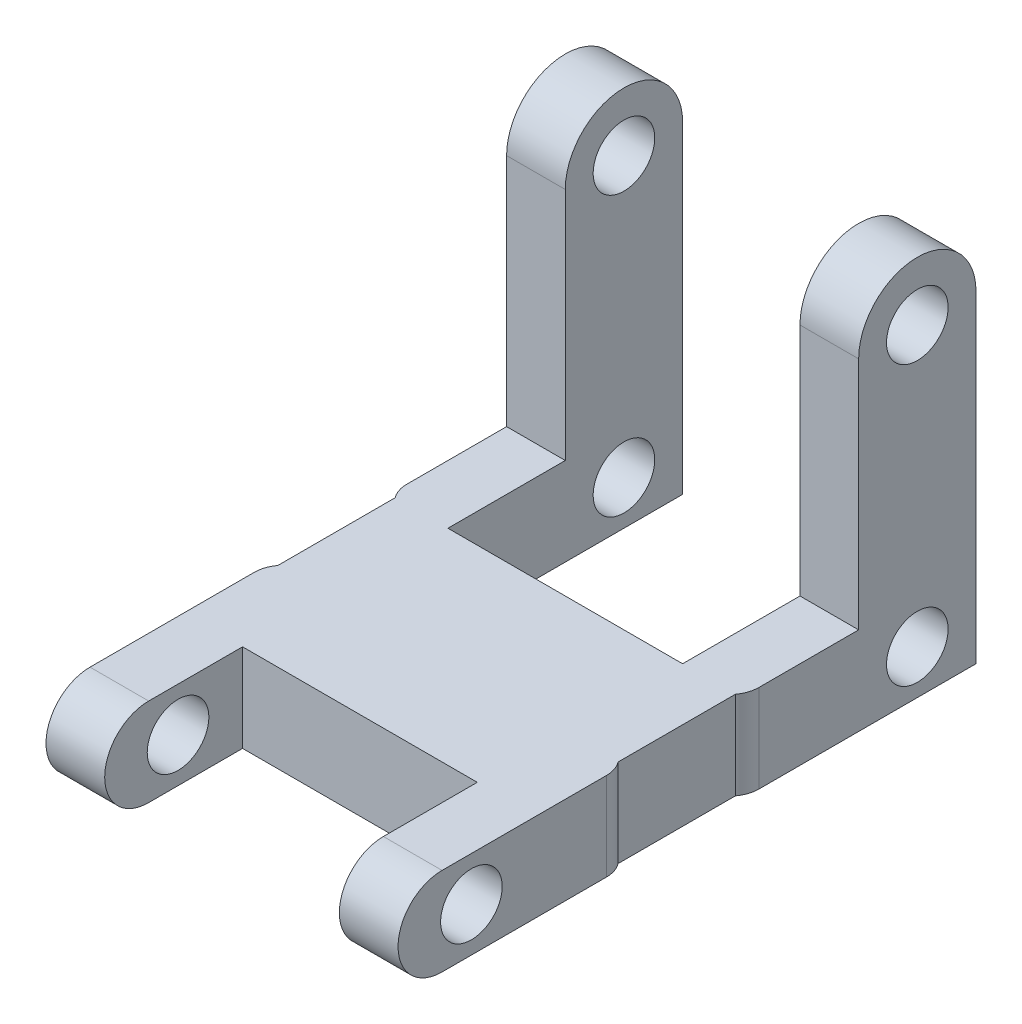
SolidWorks part; units mm, degrees
ref_plane "前视基准面" through (0, 0, 0) normal (0, 0, 1) x (1, 0, 0)
ref_plane "上视基准面" through (0, 0, 0) normal (0, 1, 0) x (1, 0, 0)
ref_plane "右视基准面" through (0, 0, 0) normal (1, 0, 0) x (0, 0, -1)
other "Configuration Table"
sketch "草图1" plane through (0, 0, 0) normal (0, 1, 0) x (1, 0, 0)
  line L0 (-6, 0) -> (6, 0)
  line L1 (-6, 0) -> (-6, -8.7)
  line L2 (-6, -8.7) -> (-4, -8.7)
  line L3 (-4, -8.7) -> (-4, -3)
  line L4 (-4, -3) -> (4, -3)
  line L5 (4, -3) -> (4, -8.7)
  line L6 (4, -8.7) -> (6, -8.7)
  line L7 (6, -8.7) -> (6, 0)
  point P4 (0, 0)
  dimension "D1" = 8.7
  dimension "D2" = 2
  dimension "D3" = 5.7
  dimension "D4" = 8
  dimension "D5" = 5.7
  dimension "D6" = 5.7
  dimension "D7" = 8.7
  dimension "D8" = 2
extrude "凸台-拉伸1" add sketch "草图1" along normal blind 3
sketch "草图2" plane through (-6, 0, 0) normal (-1, 0, 0) x (0, 0, 1)
  line L2 (6.2, 3) -> (0, 3)
  line L3 (0, 3) -> (0, 0)
  line L4 (0, 0) -> (6.2, 0)
  arc A0 (6.2, 0) -> (6.2, 3) centre (6.2, 1.5) ccw
  dimension "D2" = 3
  dimension "D1" = 1.5
  dimension "D3" = 6.2
extrude "切除-拉伸1" cut sketch "草图2" against normal blind 12 flip side to cut
sketch "草图3" plane through (-6, 0, 0) normal (-1, 0, 0) x (0, 0, 1)
  line L0 (6.2, 1.5) -> (5.2, 1.5) construction
  circle A2 centre (5.2, 1.5) radius 1.05
  dimension "D3" = 2.1
  dimension "D2" = 1
extrude "切除-拉伸2" cut sketch "草图3" against normal blind 12
sketch "草图4" plane through (0, 0, 0) normal (0, 0, -1) x (-1, 0, 0)
  line L0 (0, 3) -> (0, 0) construction
  line L1 (-6, 3) -> (6, 3) construction
  circle A0 centre (0, 1.5) radius 0.95
  dimension "D1" = 1.9
extrude "凸台-拉伸2" add sketch "草图4" along normal blind 4
ref_plane "基准面1" through (0, 0, -4) normal (0, 0, -1) x (-1, 0, 0)
sketch "草图5" plane through (0, 0, -4) normal (0, 0, -1) x (-1, 0, 0)
  line L1 (6, 3) -> (6, 0)
  line L15 (6, 3) -> (-6, 3)
  line L16 (-6, 3) -> (-6, 0)
  line L17 (-6, 3) -> (-6, 0) construction
  line L18 (-6, 3) -> (-6, 0) construction
  line L19 (-6, 0) -> (6, 0)
extrude "凸台-拉伸3" add sketch "草图5" along normal blind 8
sketch "草图6" plane through (6, 0, 0) normal (1, 0, 0) x (0, 0, -1)
  line L0 (12, 1.5) -> (10, 1.5) construction
  line L1 (12, 3) -> (12, 0) construction
  circle A1 centre (10, 1.5) radius 1.05
  dimension "D3" = 2.1
  dimension "D1" = 2
extrude "切除-拉伸3" cut sketch "草图6" against normal blind 12
sketch "草图8" plane through (0, 3, 0) normal (0, 1, 0) x (1, 0, 0)
  line L0 (-6, 12) -> (-4, 12) construction
  line L1 (-6, 12) -> (6, 12) construction
  line L2 (-4, 12) -> (4, 12)
  line L4 (-4, 8) -> (4, 8)
  line L8 (-4, 12) -> (-4, 8)
  line L9 (4, 12) -> (4, 8)
  line L10 (6, 12) -> (4, 12) construction
  dimension "D1" = 2
  dimension "D2" = 2
extrude "切除-拉伸4" cut sketch "草图8" against normal blind 8
sketch "草图9" plane through (0, 3, 0) normal (0, 1, 0) x (1, 0, 0)
  line L1 (-3.5, 12) -> (-1.5, 12)
  line L7 (-1.5, 12) -> (-1.5, 9)
  line L9 (-1.5, 9) -> (-3.5, 9)
  line L11 (-3.5, 9) -> (-3.5, 12)
  point P0 (-3.5, 10.5)
  dimension "D1" = 3
  dimension "D2" = 2
  dimension "D3" = 9
  dimension "D4" = 1.5
  dimension "D5" = 10.5
sketch "草图10" plane through (-6, 0, 0) normal (-1, 0, 0) x (0, 0, 1)
  line L3 (-12, 3) -> (-8, 3)
  line L6 (-8, 3) -> (-8, 11)
  line L7 (-12, 3) -> (-12, 11)
  arc A1 (-8, 11) -> (-12, 11) centre (-10, 11) ccw
  dimension "D2" = 8
  dimension "D3" = 2
  dimension "D1" = 4
extrude "凸台-拉伸5" add sketch "草图10" against normal blind 2
sketch "草图11" plane through (-4, 0, 0) normal (-1, 0, 0) x (0, 0, 1)
  circle A2 centre (-10, 11) radius 1.05
  dimension "D1" = 2.1
mirror "镜向1" about plane through (0, 0, 0) normal (1, 0, 0) of "凸台-拉伸5"
sketch "草图12" plane through (0, 0, -4) normal (0, 0, 1) x (1, 0, 0)
  line L4 (6, 3) -> (5.8, 3) construction
  line L5 (-6, 3) -> (6, 3) construction
  line L6 (-6, 3) -> (-5.8, 3) construction
  line L7 (-5.8, 3) -> (5.8, 3)
  line L8 (5.8, 3) -> (5.8, 0)
  line L9 (6, 0) -> (-6, 0) construction
  line L10 (5.8, 0) -> (-5.8, 0)
  line L11 (-5.8, 0) -> (-5.8, 3)
  dimension "D1" = 0.2
  dimension "D2" = 0.2
extrude "凸台-拉伸8" add sketch "草图12" along normal up to surface (4 mm away) up to face at (-0.95, 1.5, 0)
fillet "圆角1" radius 1 2 edges at (6, 1.5, 0) (-6, 1.5, 0)
sketch "草图13" plane through (0, 3, 0) normal (0, 1, 0) x (1, 0, 0)
  line L0 (-4, 8) -> (-4, 4)
  line L1 (-4, 4) -> (4, 4)
  line L2 (4, 4) -> (4, 8)
  line L3 (4, 8) -> (-4, 8)
  dimension "D1" = 4
extrude "切除-拉伸5" cut sketch "草图13" against normal blind 10
fillet "圆角2" radius 1 2 edges at (-6, 1.5, -4) (6, 1.5, -4)
extrude "切除-拉伸6" cut sketch "草图11" against normal through all both and the other way through all contours A2
